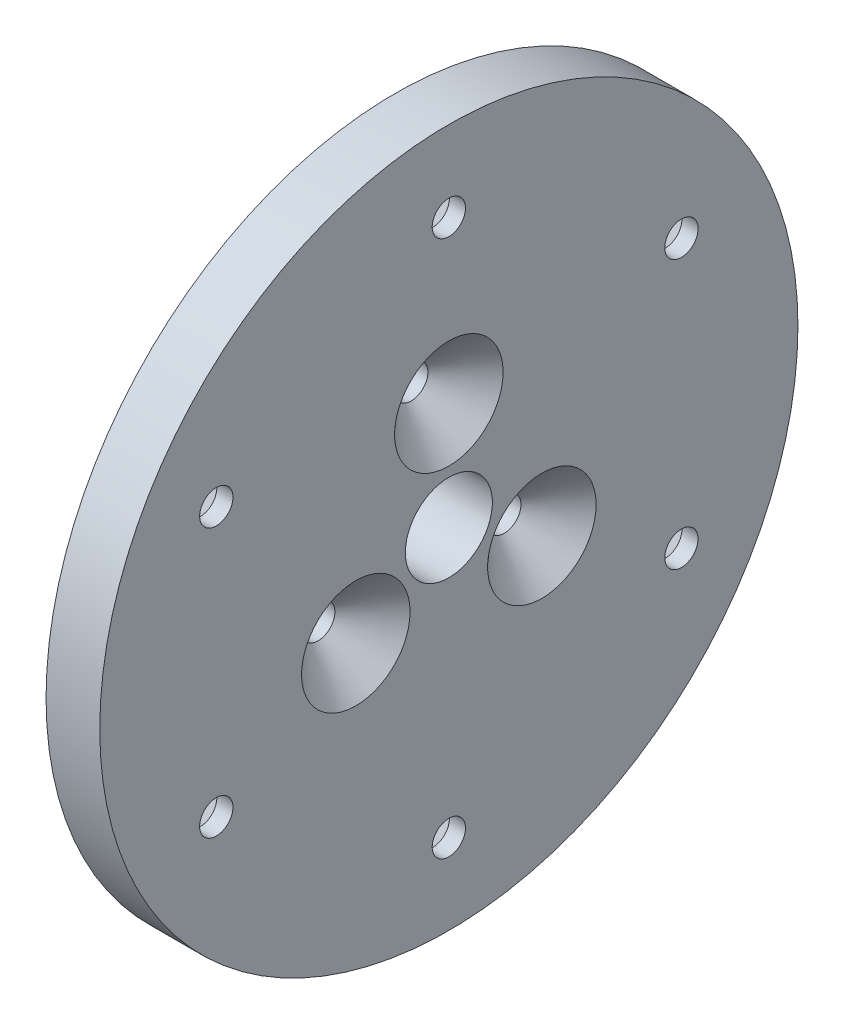
SolidWorks part; units mm, degrees
ref_plane "Ebene vorne" through (0, 0, 0) normal (0, 0, 1) x (1, 0, 0)
ref_plane "Ebene oben" through (0, 0, 0) normal (0, 1, 0) x (1, 0, 0)
ref_plane "Ebene rechts" through (0, 0, 0) normal (1, 0, 0) x (0, 0, -1)
sketch "Skizze1" plane through (0, 0, 0) normal (0, 0, 1) x (1, 0, 0)
  line L0 (0, 0) -> (-12136.2511, 0) construction
  line L1 (0, 0) -> (0, 17.25)
  line L2 (0, 17.25) -> (3, 17.25)
  line L3 (3, 17.25) -> (3, 32.5)
  line L4 (3, 32.5) -> (8, 32.5)
  line L5 (8, 32.5) -> (8, 0)
  line L6 (8, 0) -> (0, 0)
  dimension "D1" = 3
  dimension "D2" = 34.5
  dimension "D3" = 65
  dimension "D4" = 5
revolve "Rotation1" add sketch "Skizze1" angle 360 about L0
hole_wizard "Ø8.1 (8.1) Durchmesser Bohrung1" positions "Skizze2" profile "Skizze3" hole size "Ø8.1" standard "ISO" end condition through all
sketch "Skizze2" plane through (0, 0, 0) normal (-1, 0, 0) x (0, 0, 1)
  point P2 (0, 0)
sketch "Skizze3" plane through (0, 0, 0) normal (0, 1, 0) x (0, 0, 1)
  line L0 (0, 0) -> (0, 8)
  line L1 (0, 8) -> (4.05, 8)
  line L2 (4.05, 8) -> (4.05, 0)
  line L5 (4.05, 0) -> (0, 0)
  line L11 (0, -6.35) -> (0, 107.95) construction
  dimension "Bohrerdurchmesser" = 8.1
  dimension "Bohrungstiefe" = 8
sketch "Skizze4" plane through (8, 0, 0) normal (1, 0, 0) x (0, 0, -1)
  line L0 (0, 0) -> (0, 50000) construction
  circle A0 centre (0, 0) radius 10 construction
  circle A1 centre (0, 10) radius 1.55
  circle A2 centre (8.6603, -5) radius 1.55
  circle A3 centre (-8.6603, -5) radius 1.55
  point P15 (0, 0)
  dimension "D1" = 20
  dimension "D2" = 3.1
  dimension "D3" = 3
extrude "Schnitt-Linear austragen1" cut sketch "Skizze4" against normal through all
chamfer "Fase1" distance 3.5 angle 45 3 edges at (8, -5, -10.2103) (8, -5, 7.1103) (8, 10, -1.55)
sketch "Skizze5" plane through (8, 0, 0) normal (1, 0, 0) x (0, 0, -1)
  line L0 (0, 0) -> (0, -50000) construction
  circle A0 centre (0, 0) radius 25 construction
  circle A1 centre (0, 25) radius 1.55
  circle A2 centre (21.6506, 12.5) radius 1.55
  circle A3 centre (21.6506, -12.5) radius 1.55
  circle A4 centre (0, -25) radius 1.55
  circle A5 centre (-21.6506, -12.5) radius 1.55
  circle A6 centre (-21.6506, 12.5) radius 1.55
  point P20 (0, 0)
  dimension "D1" = 3.1
  dimension "D2" = 50
  dimension "D3" = 6
extrude "Schnitt-Linear austragen2" cut sketch "Skizze5" against normal through all
chamfer "Fase2" distance 3.5 angle 45 6 edges at (3, -12.5, -20.1006) (3, -25, 1.55) (3, -12.5, 23.2006) (3, 12.5, 23.2006) (3, 25, 1.55) (3, 12.5, -20.1006)
